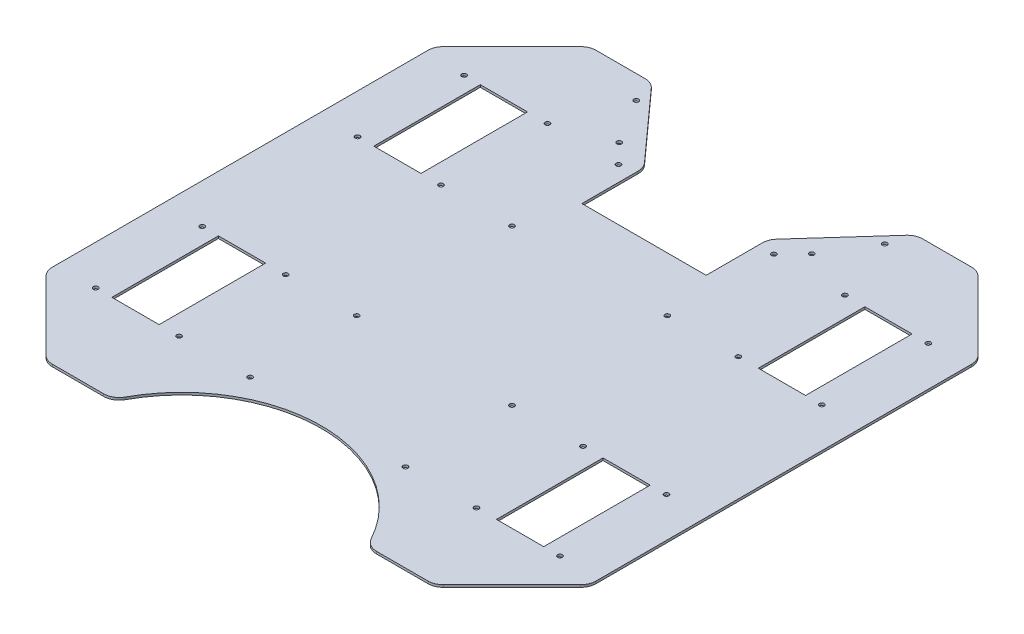
SolidWorks part; units mm, degrees
ref_plane "前视基准面" through (0, 0, 0) normal (0, 0, 1) x (1, 0, 0)
ref_plane "上视基准面" through (0, 0, 0) normal (0, 1, 0) x (1, 0, 0)
ref_plane "右视基准面" through (0, 0, 0) normal (1, 0, 0) x (0, 0, -1)
other "Configuration Table"
sketch "草图1" plane through (0, 0, 0) normal (0, 1, 0) x (1, 0, 0)
  line L0 (-125, 175) -> (-175, 125)
  line L1 (125, -175) -> (81.7103, -175)
  line L2 (175, -125) -> (175, 125)
  line L3 (125, 175) -> (85, 175)
  line L4 (-175, -125) -> (-175, 125)
  line L5 (-85, 175) -> (-40, 125)
  line L7 (125, 175) -> (175, 125)
  line L8 (175, -125) -> (125, -175)
  line L9 (-125, -175) -> (-175, -125)
  line L10 (40, 125) -> (85, 175)
  line L11 (-85, 175) -> (-125, 175)
  line L12 (40, 125) -> (40, 85)
  line L13 (40, 85) -> (-40, 85)
  line L14 (-40, 85) -> (-40, 125)
  line L15 (-138.994, 50) -> (-108.594, 50)
  line L16 (-108.594, 50) -> (-108.594, 118.58)
  line L17 (-108.594, 118.58) -> (-138.994, 118.58)
  line L18 (-138.994, 118.58) -> (-138.994, 50)
  line L19 (108.594, 50) -> (138.994, 50)
  line L20 (138.994, 50) -> (138.994, 118.58)
  line L21 (138.994, 118.58) -> (108.594, 118.58)
  line L22 (108.594, 118.58) -> (108.594, 50)
  line L23 (-175, 0) -> (175, 0) construction
  line L24 (-108.594, -118.58) -> (-138.994, -118.58)
  line L25 (-108.594, -50) -> (-108.594, -118.58)
  line L26 (-138.994, -50) -> (-108.594, -50)
  line L27 (-138.994, -118.58) -> (-138.994, -50)
  line L28 (138.994, -118.58) -> (108.594, -118.58)
  line L29 (138.994, -50) -> (138.994, -118.58)
  line L30 (108.594, -50) -> (138.994, -50)
  line L31 (108.594, -118.58) -> (108.594, -50)
  line L32 (-81.7103, -175) -> (-125, -175)
  circle A0 centre (-62, 131) radius 1.55
  circle A1 centre (-80, 160) radius 1.55
  circle A2 centre (62, 131) radius 1.55
  circle A3 centre (80, 160) radius 1.55
  circle A4 centre (-50, 118.58) radius 1.55
  circle A5 centre (-50, 50) radius 1.55
  circle A6 centre (-95.72, 50) radius 1.55
  circle A7 centre (-95.72, 118.58) radius 1.55
  circle A12 centre (-149.434, 118.58) radius 1.55
  circle A13 centre (-149.434, 50) radius 1.55
  circle A14 centre (-50, -118.58) radius 1.55
  circle A15 centre (-50, -50) radius 1.55
  circle A16 centre (-95.72, -50) radius 1.55
  circle A17 centre (-95.72, -118.58) radius 1.55
  circle A18 centre (-149.434, -50) radius 1.55
  circle A19 centre (-149.434, -118.58) radius 1.55
  circle A20 centre (50, 50) radius 1.55
  circle A21 centre (95.72, 50) radius 1.55
  circle A22 centre (95.72, 118.58) radius 1.55
  circle A23 centre (50, 118.58) radius 1.55
  circle A24 centre (149.434, 118.58) radius 1.55
  circle A25 centre (149.434, 50) radius 1.55
  circle A26 centre (149.434, -118.58) radius 1.55
  circle A27 centre (149.434, -50) radius 1.55
  circle A28 centre (95.72, -50) radius 1.55
  circle A29 centre (95.72, -118.58) radius 1.55
  circle A30 centre (50, -118.58) radius 1.55
  circle A31 centre (50, -50) radius 1.55
  arc A32 (-81.7103, -175) -> (81.7103, -175) centre (0, -212.7283) cw
  point P0 (0, 0)
  point P1 (-85, 175)
  point P2 (85, 175)
  point P3 (40, 125)
  point P4 (-40, 125)
  point P6 (125, 175)
  point P8 (175, 125)
  point P10 (175, -125)
  point P11 (125, -175)
  point P12 (-125, -175)
  point P13 (-175, -125)
  point P24 (-80, 160)
  point P25 (-62, 131)
  point P26 (62, 131)
  point P27 (80, 160)
  point P36 (-149.434, 118.58)
  point P37 (-149.434, 50)
  point P38 (-138.994, 118.58)
  point P39 (-108.594, 50)
  point P40 (-95.72, 118.58)
  point P41 (-95.72, 50)
  point P42 (-50, 118.58)
  point P43 (-50, 50)
  point P47 (-108.594, 118.58)
  point P53 (-138.994, 50)
  point P66 (-40, 85)
  point P67 (40, 85)
  point P70 (95.72, 50)
  point P71 (50, 50)
  point P72 (108.594, 50)
  point P73 (138.994, 50)
  point P74 (149.434, 50)
  point P75 (50, 118.58)
  point P76 (95.72, 118.58)
  point P77 (108.594, 118.58)
  point P78 (138.994, 118.58)
  point P81 (149.434, 118.58)
  point P85 (-50, -118.58)
  point P88 (-50, -50)
  point P91 (-95.72, -50)
  point P94 (-95.72, -118.58)
  point P101 (-149.434, -50)
  point P104 (-149.434, -118.58)
  point P118 (149.434, -118.58)
  point P121 (149.434, -50)
  point P128 (95.72, -50)
  point P131 (95.72, -118.58)
  point P134 (50, -118.58)
  point P137 (50, -50)
  point P141 (0, 0)
  dimension "D29" = 3.1
  dimension "D30" = 3.1
  dimension "D31" = 3.1
  dimension "D32" = 3.1
  dimension "D40" = 3.1
  dimension "D41" = 3.1
  dimension "D42" = 3.1
  dimension "D43" = 3.1
  dimension "D44" = 3.1
  dimension "D45" = 3.1
  dimension "D46" = 3.1
  dimension "D47" = 3.1
  dimension "D48" = 3.1
  dimension "D49" = 3.1
  dimension "D60" = 3.1
  dimension "D61" = 3.1
  dimension "D62" = 43.2897
  dimension "D63" = 90
  dimension "D1" = 175
  dimension "D2" = 175
  dimension "D3" = 125
  dimension "D4" = 125
  dimension "D5" = 125
  dimension "D6" = 125
  dimension "D7" = 125
  dimension "D8" = 125
  dimension "D9" = 125
  dimension "D10" = 125
  dimension "D11" = 175
  dimension "D12" = 175
  dimension "D13" = 40
  dimension "D14" = 40
  dimension "D15" = 85
  dimension "D16" = 85
  dimension "D17" = 125
  dimension "D18" = 125
  dimension "D19" = 40
  dimension "D20" = 45
  dimension "D21" = 160
  dimension "D22" = 160
  dimension "D23" = 80
  dimension "D24" = 80
  dimension "D25" = 62
  dimension "D26" = 131
  dimension "D27" = 62
  dimension "D28" = 131
  dimension "D33" = 50
  dimension "D34" = 118.58
  dimension "D35" = 50
  dimension "D36" = 45.72
  dimension "D37" = 12.874
  dimension "D38" = 30.4
  dimension "D39" = 10.44
  dimension "D50" = 40
  dimension "D51" = 40
  dimension "D52" = 85
  dimension "D53" = 85
  dimension "D54" = 138.013
  dimension "D55" = 50
  dimension "D56" = 45.72
  dimension "D57" = 12.874
  dimension "D58" = 30.4
  dimension "D59" = 10.44
  dimension "D64" = 0
extrude "凸台-拉伸1" add sketch "草图1" along normal blind 1.5 contours A1 | A0 | L8 L1 A32 L32 L9 L4 L0 L11 L5 L14 L13 L12 L10 L3 L7 L2 | A5 | A3 | A2 | A4 | A7 | A12 | L16 L17 L18 L15 | A6 | L21 L22 L19 L20 | A13 | A16 | A17 | A14 | A15 | A18 | A19 | L25 L24 L27 L26 | A20 | A21 | A22 | A23 | A24 | A25 | A28 | A26 | A27 | L28 L31 L30 L29 | A30 | A31 | A29
fillet "圆角1" radius 10 1 edges at (-40, 0.75, -125)
fillet "圆角2" radius 10 1 edges at (40, 0.75, -125)
fillet "圆角3" radius 10 12 edges at (-85, 0.75, -175) (85, 0.75, -175) (125, 0.75, -175) (175, 0.75, -125) (175, 0.75, 125) (125, 0.75, 175) (81.7103, 0.75, 175) (-81.7103, 0.75, 175) (-125, 0.75, 175) (-175, 0.75, 125) (-175, 0.75, -125) (-125, 0.75, -175)
